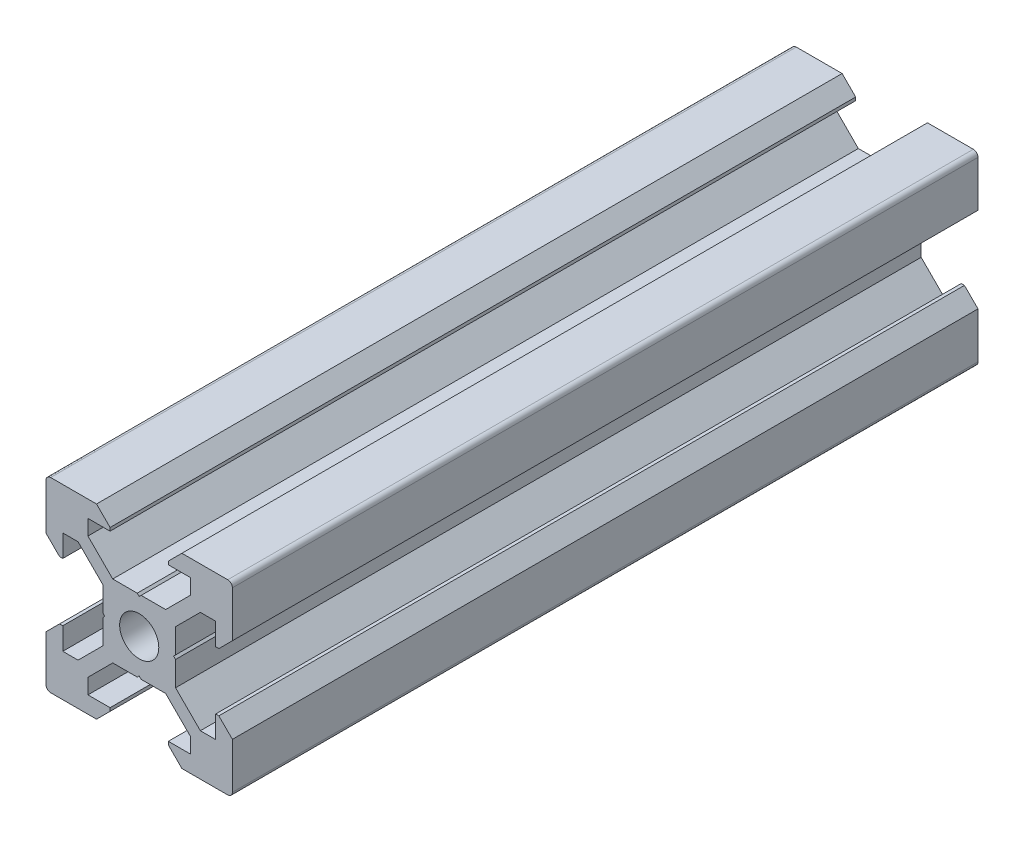
SolidWorks part; units mm, degrees
material "6061-T6 (SS)"
ref_plane "Front Plane" through (0, 0, 0) normal (0, 0, 1) x (1, 0, 0)
ref_plane "Top Plane" through (0, 0, 0) normal (0, 1, 0) x (1, 0, 0)
ref_plane "Right Plane" through (0, 0, 0) normal (1, 0, 0) x (0, 0, -1)
sketch "Sketch1" plane through (0, 0, 0) normal (0, 0, 1) x (1, 0, 0)
  line L1 (9.5, -10) -> (-9.5, -10)
  line L2 (10, -9.5) -> (10, 9.5)
  line L3 (9.5, 10) -> (-9.5, 10)
  line L4 (-10, -9.5) -> (-10, 9.5)
  line L5 (10, -10) -> (-10, 10) construction
  line L6 (10, 10) -> (-10, -10) construction
  circle A0 centre (0, 0) radius 2.1
  arc A1 (-9.5, 10) -> (-10, 9.5) centre (-9.5, 9.5) ccw
  arc A2 (10, 9.5) -> (9.5, 10) centre (9.5, 9.5) ccw
  arc A3 (9.5, -10) -> (10, -9.5) centre (9.5, -9.5) ccw
  arc A4 (-9.5, -10) -> (-10, -9.5) centre (-9.5, -9.5) cw
  point P0 (0, 0)
  line B0 (0, 0) -> (0, 10) construction
  line B1 (0, 3.69) -> (-0.21, 3.9)
  line B2 (-0.21, 3.9) -> (-2.8393, 3.9)
  line B3 (-2.8393, 3.9) -> (-5.5, 6.5607)
  line B4 (-5.5, 6.5607) -> (-5.5, 8.2)
  line B5 (-5.5, 8.2) -> (-3.125, 8.2)
  line B6 (-3.125, 8.2) -> (-3.125, 8.545)
  line B7 (-3.125, 8.545) -> (-4.58, 10)
  line B8 (-4.58, 10) -> (4.58, 10)
  line B9 (0, 0) -> (-5.9132, 5.9132) construction
  line B10 (3.125, 8.545) -> (4.58, 10)
  line B11 (3.125, 8.2) -> (3.125, 8.545)
  line B12 (5.5, 8.2) -> (3.125, 8.2)
  line B13 (5.5, 6.5607) -> (5.5, 8.2)
  line B14 (2.8393, 3.9) -> (5.5, 6.5607)
  line B15 (0.21, 3.9) -> (2.8393, 3.9)
  line B16 (0, 3.69) -> (0.21, 3.9)
  line B17 (0, 0) -> (-10, 0) construction
  line B18 (-3.69, 0) -> (-3.9, -0.21)
  line B19 (-3.9, -0.21) -> (-3.9, -2.8393)
  line B20 (-3.9, -2.8393) -> (-6.5607, -5.5)
  line B21 (-6.5607, -5.5) -> (-8.2, -5.5)
  line B22 (-8.2, -5.5) -> (-8.2, -3.125)
  line B23 (-8.2, -3.125) -> (-8.545, -3.125)
  line B24 (-8.545, -3.125) -> (-10, -4.58)
  line B25 (-10, -4.58) -> (-10, 4.58)
  line B26 (0, 0) -> (-5.9132, -5.9132) construction
  line B27 (-8.545, 3.125) -> (-10, 4.58)
  line B28 (-8.2, 3.125) -> (-8.545, 3.125)
  line B29 (-8.2, 5.5) -> (-8.2, 3.125)
  line B30 (-6.5607, 5.5) -> (-8.2, 5.5)
  line B31 (-3.9, 2.8393) -> (-6.5607, 5.5)
  line B32 (-3.9, 0.21) -> (-3.9, 2.8393)
  line B33 (-3.69, 0) -> (-3.9, 0.21)
  line B34 (0, 0) -> (0, -10) construction
  line B35 (0, -3.69) -> (0.21, -3.9)
  line B36 (0.21, -3.9) -> (2.8393, -3.9)
  line B37 (2.8393, -3.9) -> (5.5, -6.5607)
  line B38 (5.5, -6.5607) -> (5.5, -8.2)
  line B39 (5.5, -8.2) -> (3.125, -8.2)
  line B40 (3.125, -8.2) -> (3.125, -8.545)
  line B41 (3.125, -8.545) -> (4.58, -10)
  line B42 (4.58, -10) -> (-4.58, -10)
  line B43 (0, 0) -> (5.9132, -5.9132) construction
  line B44 (-3.125, -8.545) -> (-4.58, -10)
  line B45 (-3.125, -8.2) -> (-3.125, -8.545)
  line B46 (-5.5, -8.2) -> (-3.125, -8.2)
  line B47 (-5.5, -6.5607) -> (-5.5, -8.2)
  line B48 (-2.8393, -3.9) -> (-5.5, -6.5607)
  line B49 (-0.21, -3.9) -> (-2.8393, -3.9)
  line B50 (0, -3.69) -> (-0.21, -3.9)
  line B51 (0, 0) -> (10, 0) construction
  line B52 (3.69, 0) -> (3.9, 0.21)
  line B53 (3.9, 0.21) -> (3.9, 2.8393)
  line B54 (3.9, 2.8393) -> (6.5607, 5.5)
  line B55 (6.5607, 5.5) -> (8.2, 5.5)
  line B56 (8.2, 5.5) -> (8.2, 3.125)
  line B57 (8.2, 3.125) -> (8.545, 3.125)
  line B58 (8.545, 3.125) -> (10, 4.58)
  line B59 (10, 4.58) -> (10, -4.58)
  line B60 (0, 0) -> (5.9132, 5.9132) construction
  line B61 (8.545, -3.125) -> (10, -4.58)
  line B62 (8.2, -3.125) -> (8.545, -3.125)
  line B63 (8.2, -5.5) -> (8.2, -3.125)
  line B64 (6.5607, -5.5) -> (8.2, -5.5)
  line B65 (3.9, -2.8393) -> (6.5607, -5.5)
  line B66 (3.9, -0.21) -> (3.9, -2.8393)
  line B67 (3.69, 0) -> (3.9, -0.21)
  dimension "D1" = 4.2
  dimension "D3" = 0.5
  dimension "D2" = 20
sketch_block_instance "V Slot 1-4"
sketch_block "V Slot 1" parameters "D1"=10, "D2"=11, "D3"=4.3, "D4"=1.8, "D5"=0.21, "D6"=45, "D7"=9.16, "D8"=1.5, "D9"=6.25
sketch_block_instance "V Slot 1-5"
sketch_block_instance "V Slot 1-6"
sketch_block_instance "V Slot 1-7"
extrude "Boss-Extrude1" add sketch "Sketch1" along normal blind 80 contours B67 B52 B53 B54 B55 B56 B57 B58 L2 A2 L3 B10 B11 B12 B13 B14 B15 B16 B1 B2 B3 B4 B5 B6 B7 A1 L4 B27 B28 B29 B30 B31 B32 B33 B18 B19 B20 B21 B22 B23 B24 A4 L1 B44 B45 B46 B47 B48 B49 region at (7.04, -9.7172, 0)
